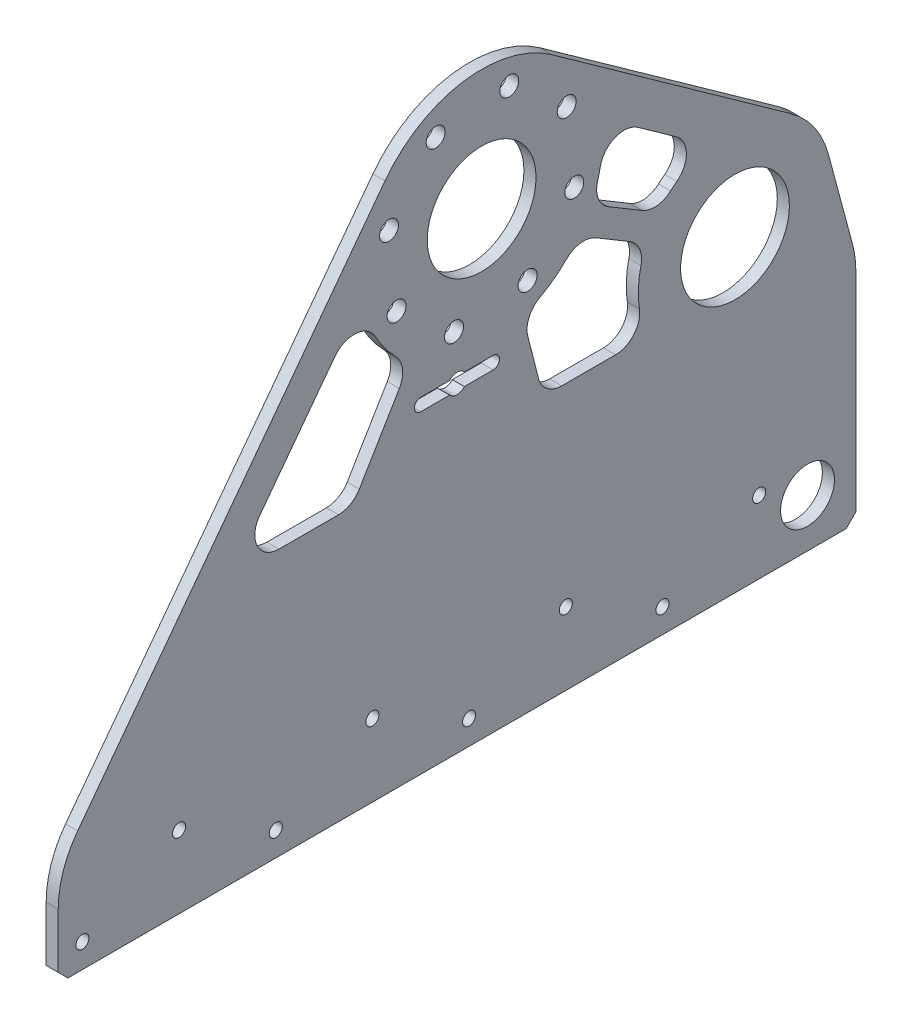
SolidWorks part; units mm, degrees
material "6061-T6 (SS)"
ref_plane "Front Plane" through (0, 0, 0) normal (0, 0, 1) x (1, 0, 0)
ref_plane "Top Plane" through (0, 0, 0) normal (0, 1, 0) x (1, 0, 0)
ref_plane "Right Plane" through (0, 0, 0) normal (1, 0, 0) x (0, 0, -1)
sketch "Sketch1" plane through (0, 0, 0) normal (1, 0, 0) x (0, 0, -1)
  line L0 (0, -25.4) -> (0, 31.864)
  line L13 (-209.55, -25.4) -> (0, -25.4)
  line L14 (-209.55, -25.4) -> (-209.55, -8.4756)
  line L15 (-204.4603, 6.7773) -> (-123.6994, 114.3161)
  line L16 (-209.55, 0) -> (0, 0) construction
  line L17 (-7.2155, 62.1365) -> (-0.8655, 38.438)
  line L18 (-79.8716, 121.0963) -> (-16.9981, 76.2396)
  circle A5 centre (-31.75, 55.5625) radius 14.2875
  circle A6 centre (-98.3115, 95.25) radius 14.2875 construction
  arc A7 (-79.8716, 121.0963) -> (-123.6994, 114.3161) centre (-98.3115, 95.25) ccw
  arc A8 (-16.9981, 76.2396) -> (-7.2155, 62.1365) centre (-31.75, 55.5625) cw
  circle A9 centre (-98.3115, 95.25) radius 14.2875
  arc A10 (-209.55, -8.4756) -> (-204.4603, 6.7773) centre (-184.15, -8.4756) cw
  arc A11 (-0.8655, 38.438) -> (0, 31.864) centre (-25.4, 31.864) cw
  point P4 (0, 0)
  dimension "D4" = 31.75
  dimension "D7" = 25.4
  dimension "D10" = 28.575
  dimension "D3" = 41.275
  dimension "D9" = 25.4
  dimension "D12" = 77.4954
  dimension "D13" = 63.5
  dimension "D14" = 63.5
  dimension "D5" = 25.4
  dimension "D8" = 28.575
  dimension "D2" = 15
  dimension "D6" = 209.55
extrude "Boss-Extrude1" add sketch "Sketch1" along normal blind 3.175
hole_wizard "#10 Clearance Hole1" positions "Sketch2" profile "Sketch3" hole size "#10" standard "ANSI Inch" end condition through all
sketch "Sketch2" plane through (3.175, 0, 0) normal (1, 0, 0) x (0, 0, -1)
  line L0 (-98.3115, 95.25) -> (-31.75, 55.5625) construction
  line L1 (-72.9115, 95.25) -> (-86.2351, 72.9046) construction
  circle A0 centre (-98.3115, 95.25) radius 25.4 construction
  circle A1 centre (-31.75, 55.5625) radius 14.2875 construction
  point P17 (-91.0503, 119.59)
  point P38 (-75.9661, 107.3265)
  point P39 (-73.9716, 87.9887)
  point P40 (-86.2351, 72.9046)
  point P41 (-105.5728, 70.91)
  point P42 (-120.657, 83.1735)
  point P43 (-122.6515, 102.5113)
  point P44 (-110.388, 117.5954)
  dimension "D1" = 50.8
  dimension "D2" = 8
sketch "Sketch3" plane through (3.175, 119.59, 91.0503) normal (0, 1, 0) x (0, 0, -1)
  line L0 (0, 0) -> (0, 3.175)
  line L1 (0, 3.175) -> (2.4892, 3.175)
  line L2 (2.4892, 3.175) -> (2.4892, 0)
  line L5 (2.4892, 0) -> (0, 0)
  line L11 (0, -6.35) -> (0, 107.95) construction
  dimension "Thru Hole Dia." = 4.9784
  dimension "Thru Hole Depth" = 3.175
sketch "Sketch9" plane through (3.175, 0, 0) normal (1, 0, 0) x (0, 0, -1)
  line L0 (0, 0) -> (-208.0942, 0) construction
  line L1 (0, -25.4) -> (0, 31.864) construction
  line L2 (0, -25.4) -> (0, 31.864) construction
  line L3 (-209.55, -25.4) -> (0, -25.4) construction
  line L4 (-164.2565, 44.45) -> (-129.699, 90.4657)
  line L5 (-123.6994, 114.3161) -> (-204.4603, 6.7773) construction
  line L6 (-176.1684, 44.45) -> (-132.2977, 44.45) construction
  line L7 (-164.2565, 44.45) -> (-132.2977, 44.45)
  line L8 (-66.9456, 100.1737) -> (-38.6711, 80.0014)
  line L9 (-16.9981, 76.2396) -> (-79.8716, 121.0963) construction
  line L10 (-69.5519, 81.7985) -> (-51.7692, 71.1955)
  line L11 (-55.0212, 65.7415) -> (-72.8039, 76.3444)
  line L12 (-98.3115, 95.25) -> (-31.75, 55.5625) construction
  line L13 (-98.3115, 95.25) -> (-132.7027, 37.5711) construction
  line L14 (-98.3115, 95.25) -> (-81.8784, 30.2801) construction
  line L15 (-117.2171, 69.7423) -> (-132.2977, 44.45)
  line L16 (-124.9046, 44.45) -> (-111.763, 66.4903) construction
  line L17 (-93.6431, 63.8451) -> (-88.7375, 44.45) construction
  line L18 (-82.1875, 44.45) -> (-87.487, 65.4022)
  line L19 (-82.1875, 44.45) -> (0, 44.45) construction
  line L20 (-82.1875, 44.45) -> (-54.5901, 44.45)
  line L21 (-124.9046, 44.45) -> (-88.7375, 44.45) construction
  line L22 (-124.9046, 44.45) -> (-88.7375, 44.45) construction
  circle A0 centre (-12.7, -12.7) radius 7.0739
  arc A2 (-204.4603, 6.7773) -> (-209.55, -8.4756) centre (-184.15, -8.4756) ccw construction
  arc A3 (-69.5519, 81.7985) -> (-117.2171, 69.7423) centre (-98.3115, 95.25) ccw construction
  arc A4 (-79.8716, 121.0963) -> (-123.6994, 114.3161) centre (-98.3115, 95.25) ccw construction
  arc A5 (-55.0212, 65.7415) -> (-51.7692, 71.1955) centre (-31.75, 55.5625) ccw construction
  arc A6 (-7.2155, 62.1365) -> (-16.9981, 76.2396) centre (-31.75, 55.5625) ccw construction
  arc A7 (-129.699, 90.4657) -> (-117.2171, 69.7423) centre (-98.3115, 95.25) ccw
  arc A8 (-54.5901, 44.45) -> (-55.0212, 65.7415) centre (-31.75, 55.5625) cw
  arc A9 (-51.7692, 71.1955) -> (-38.6711, 80.0014) centre (-31.75, 55.5625) cw
  arc A10 (-69.5519, 81.7985) -> (-66.9456, 100.1737) centre (-98.3115, 95.25) ccw
  arc A11 (-87.487, 65.4022) -> (-72.8039, 76.3444) centre (-98.3115, 95.25) ccw construction
  arc A12 (-87.487, 65.4022) -> (-72.8039, 76.3444) centre (-98.3115, 95.25) ccw
  arc A13 (-111.763, 66.4903) -> (-93.6431, 63.8451) centre (-98.3115, 95.25) ccw construction
  arc A14 (-111.763, 66.4903) -> (-93.6431, 63.8451) centre (-98.3115, 95.25) ccw construction
  dimension "D1" = 14.1478
  dimension "D3" = 12.7
  dimension "D2" = 12.7
  dimension "D4" = 9.525
  dimension "D5" = 44.45
  dimension "D6" = 9.525
  dimension "D7" = 6.35
  dimension "D8" = 6.35
  dimension "D9" = 6.35
  dimension "D10" = 45
  dimension "D11" = 45
extrude "Cut-Extrude1" cut sketch "Sketch9" against normal through all
fillet "Fillet1" radius 6.35 13 edges at (1.5875, 100.1737, 66.9456) (1.5875, 71.1955, 51.7692) (1.5875, 81.7985, 69.5519) (1.5875, 80.0014, 38.6711) (1.5875, 76.3444, 72.8039) (1.5875, 65.7415, 55.0212) (1.5875, 44.45, 82.1875) (1.5875, 65.4022, 87.487) (1.5875, 44.45, 54.5901) (1.5875, 44.45, 164.2565) (1.5875, 90.4657, 129.699) (1.5875, 69.7423, 117.2171) (1.5875, 44.45, 132.2977)
hole_wizard "1/8 (0.135) Diameter Hole1" positions "Sketch10" profile "Sketch11" hole size "1/8" standard "ANSI Inch" end condition through all
sketch "Sketch10" plane through (3.175, 0, 0) normal (1, 0, 0) x (0, 0, -1)
  point P4 (-177.8, -6.35)
  point P7 (-152.4, -19.05)
  point P10 (-127, -6.35)
  point P13 (-101.6, -19.05)
  point P16 (-76.2, -6.35)
  point P19 (-50.8, -19.05)
  point P22 (-25.4, -6.35)
  point P26 (-203.2, -19.05)
sketch "Sketch11" plane through (3.175, -6.35, 177.8) normal (0, 1, 0) x (0, 0, -1)
  line L0 (0, 0) -> (0, 3.175)
  line L1 (0, 3.175) -> (1.7145, 3.175)
  line L2 (1.7145, 3.175) -> (1.7145, 0)
  line L5 (1.7145, 0) -> (0, 0)
  line L11 (0, -6.35) -> (0, 107.95) construction
  dimension "Thru Hole Dia." = 3.429
  dimension "Thru Hole Depth" = 3.175
chamfer "Chamfer1" distance 2.54 angle 45 2 edges at (1.5875, -25.4, 0) (1.5875, -25.4, 209.55)
sketch "Sketch12" plane through (3.175, 0, 0) normal (1, 0, 0) x (0, 0, -1)
  line L5 (-102.8431, 60.3885) -> (-95.265, 60.3885)
  line L6 (-114.315, 58.7375) -> (-95.265, 58.7375) construction
  line L7 (-102.8431, 57.0865) -> (-95.265, 57.0865)
  line L8 (-114.315, 60.3885) -> (-106.7369, 60.3885)
  line L11 (-114.315, 57.0865) -> (-106.7369, 57.0865)
  line L12 (-95.265, 60.325) -> (-95.265, 57.15) construction
  line L13 (-341.2998, 60.325) -> (-114.315, 60.325) construction
  line L14 (-341.2998, 57.15) -> (-114.315, 57.15) construction
  line L15 (-114.315, 58.7375) -> (-123.7788, 58.7375) construction
  line L16 (-130.4505, 47.548) -> (-119.931, 65.1907) construction
  line L17 (-95.265, 58.7375) -> (-85.8013, 58.7375) construction
  line L18 (-86.1876, 60.2647) -> (-83.3998, 49.2429) construction
  arc A2 (-102.8431, 60.3885) -> (-106.7369, 60.3885) centre (-104.79, 58.7375) ccw
  arc A3 (-114.315, 60.3885) -> (-114.315, 57.0865) centre (-114.315, 58.7375) ccw
  arc A4 (-95.265, 57.0865) -> (-95.265, 60.3885) centre (-95.265, 58.7375) ccw
  arc A5 (-106.7369, 57.0865) -> (-102.8431, 57.0865) centre (-104.79, 58.7375) ccw
  point P3 (-104.79, 58.7375)
  dimension "D3" = 5.1054
  dimension "D1" = 3.302
  dimension "D2" = 19.05
extrude "Cut-Extrude2" cut sketch "Sketch12" against normal through all
